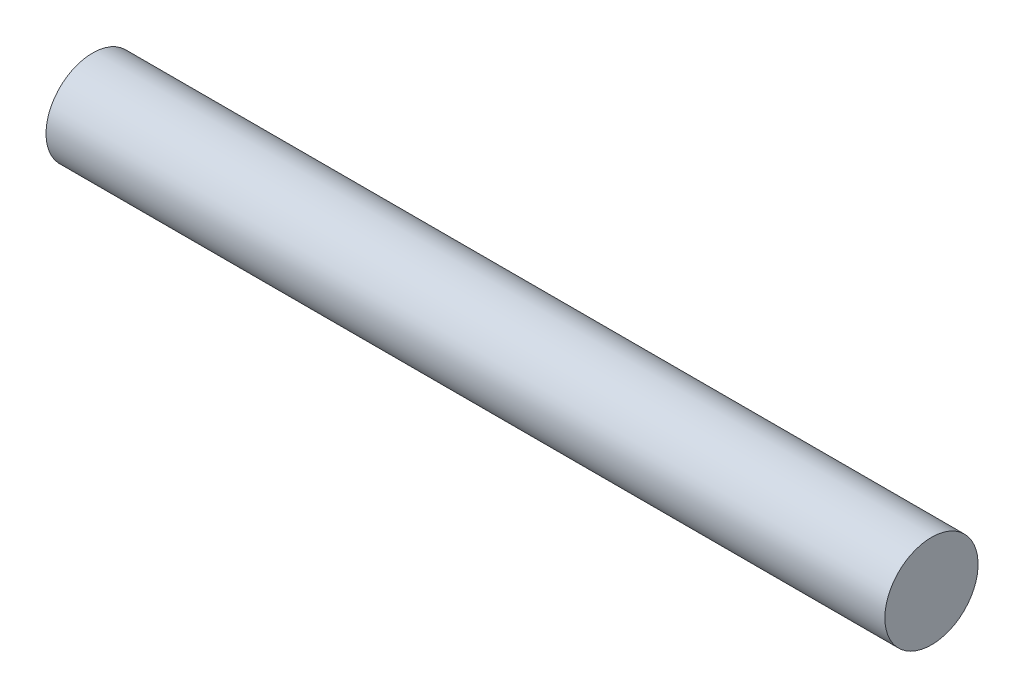
SolidWorks part; units mm, degrees
ref_plane "Front" through (0, 0, 0) normal (0, 0, 1) x (1, 0, 0)
ref_plane "Top" through (0, 0, 0) normal (0, 1, 0) x (1, 0, 0)
ref_plane "Right" through (0, 0, 0) normal (1, 0, 0) x (0, 0, -1)
sketch "Sketch1" plane through (0, 0, 0) normal (1, 0, 0) x (0, 0, -1)
  circle A0 centre (0, 0) radius 10
  dimension "D1" = 20
extrude "Boss-Extrude1" add sketch "Sketch1" along normal blind 180
